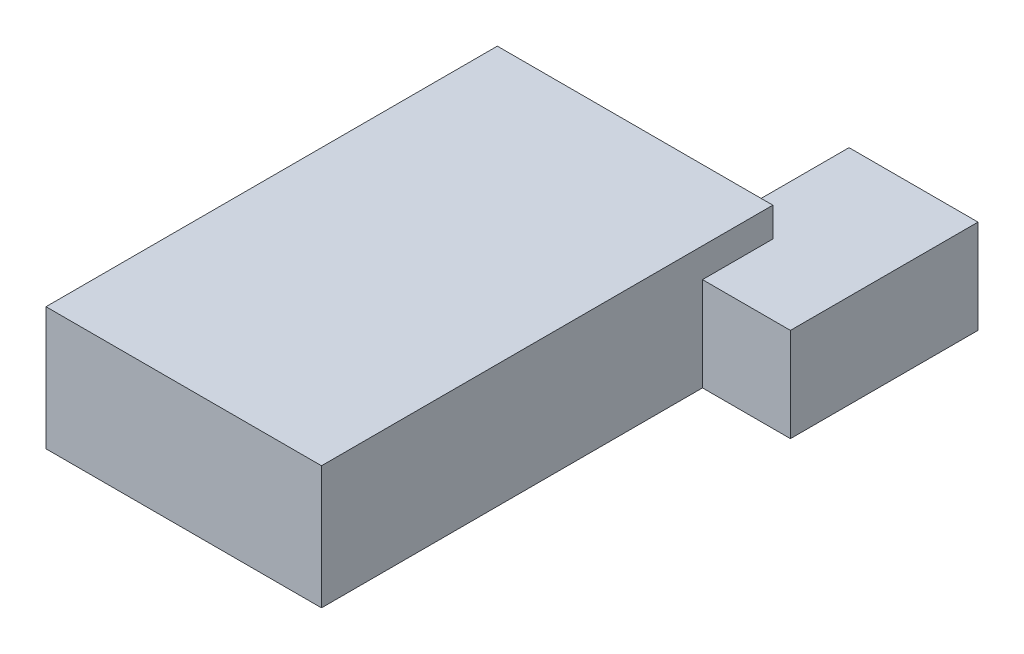
SolidWorks part; units mm, degrees
ref_plane "Front Plane" through (0, 0, 0) normal (0, 0, 1) x (1, 0, 0)
ref_plane "Top Plane" through (0, 0, 0) normal (0, 1, 0) x (1, 0, 0)
ref_plane "Right Plane" through (0, 0, 0) normal (1, 0, 0) x (0, 0, -1)
sketch "Sketch1" plane through (0, 0, 0) normal (0, 1, 0) x (1, 0, 0)
  line L1 (-4500, -7500) -> (4500, -7500)
  line L2 (-4500, -7500) -> (-4500, 7500)
  line L3 (-4500, 7500) -> (4500, 7500)
  line L4 (4500, -7500) -> (4500, 7500)
  line L5 (-4500, -7500) -> (4500, 7500) construction
  line L6 (-4500, 7500) -> (4500, -7500) construction
  point P0 (0, 0)
  dimension "D1" = 15000
  dimension "D2" = 9000
extrude "Boss-Extrude1" add sketch "Sketch1" along normal blind 4000
sketch "Sketch2" plane through (0, 0, -7500) normal (0, 0, -1) x (-1, 0, 0)
  line L1 (-4500, 0) -> (-3500, 0)
  line L2 (-4500, 0) -> (-4500, 3000)
  line L3 (-4500, 3000) -> (-3500, 3000)
  line L4 (-3500, 0) -> (-3500, 3000)
  line L5 (-4500, 3000) -> (-7500, 3000)
  line L6 (-4500, 3000) -> (-4500, 0)
  line L7 (-4500, 0) -> (-7500, 0)
  line L8 (-7500, 3000) -> (-7500, 0)
  line M1 (-4500, 0) -> (4500, 0)
  line M4 (-4500, 4000) -> (-4500, 0)
  dimension "D1" = 4000
  dimension "D2" = 1000
  dimension "3m" = 3000
extrude "Boss-Extrude2" add sketch "Sketch2" along normal blind 4000 and the other way blind 2000 contours L5 L8 L7 M4 | L4 L3 M1 M4 region at (4000, 1500, -7500) region at (6000, 1500, -7500)
sketch "Sketch3" plane through (0, 0, 0) normal (0, -1, 0) x (1, 0, 0)
  line L0 (3500, -11500) -> (7500, -11500) construction
  line L1 (10500, -11500) -> (-500, -11500)
  line L2 (10500, -11500) -> (10500, -4500)
  line L3 (10500, -4500) -> (-500, -4500)
  line L4 (-500, -11500) -> (-500, -4500)
  point P5 (3500, -11500)
  point P12 (7500, -11500)
  dimension "D1" = 11000
  dimension "D2" = 4000
  dimension "D3" = 7000
extrude "Boss-Extrude3" add sketch "Sketch3" along normal blind 12500
sketch "Sketch4" plane through (0, -12500, 0) normal (0, -1, 0) x (1, 0, 0)
  line L1 (10500, -11500) -> (3500, -11500)
  line L2 (10500, -11500) -> (10500, -7500)
  line L3 (10500, -7500) -> (3500, -7500)
  line L4 (3500, -11500) -> (3500, -7500)
  dimension "D1" = 7000
  dimension "D2" = 4000
extrude "Boss-Extrude4" add sketch "Sketch4" along normal blind 1500
sketch "Sketch5" plane through (0, 0, -4500) normal (0, 0, 1) x (1, 0, 0)
  line L1 (-500, -12500) -> (9500, -12500)
  line L2 (-500, -12500) -> (-500, -8500)
  line L3 (-500, -8500) -> (9500, -8500)
  line L4 (9500, -12500) -> (9500, -8500)
  dimension "D1" = 10000
  dimension "D2" = 4000
extrude "Boss-Extrude5" add sketch "Sketch5" along normal blind 12000
sketch "Sketch6" plane through (9500, 0, 0) normal (1, 0, 0) x (0, 0, -1)
  line L0 (-7250, -11500) -> (-7500, -11500) construction
  line L1 (-7500, -12500) -> (-7500, -8500) construction
  line L2 (-7500, -12500) -> (4500, -12500) construction
  circle A0 centre (-5250, -11500) radius 2000
  dimension "D1" = 4000
  dimension "D2" = 1000
  dimension "D3" = 250
extrude "Boss-Extrude6" add sketch "Sketch6" along normal blind 6000
ref_plane "Plane1" through (0, -10500, 0) normal (0, -1, 0) x (-1, 0, 0)
sketch "Sketch9" plane through (0, -10500, 0) normal (0, -1, 0) x (-1, 0, 0)
  circle A0 centre (-22728.4161, -5250) radius 7500
  point P2 (-15500, -3250)
  point P3 (-15500, -7250)
  dimension "D1" = 15000
extrude "Boss-Extrude8" add sketch "Sketch9" against normal blind 4000 and the other way blind 10000
sketch "Sketch10" plane through (0, -6500, 0) normal (0, 1, 0) x (1, 0, 0)
  line L0 (15228.4161, -5250) -> (30228.4161, -5250)
  arc A0 (15500, -3250) -> (15500, -7250) centre (22728.4161, -5250) ccw construction
  circle A1 centre (22728.4161, -5250) radius 7500 construction
  arc A2 (15228.4161, -5250) -> (30228.4161, -5250) centre (22728.4161, -5250) cw
revolve "Revolve5" add sketch "Sketch10" angle 180 about L0
sketch "Sketch12" plane through (-500, 0, 0) normal (-1, 0, 0) x (0, 0, 1)
  arc A0 (3517.9492, -12500) -> (6982.0508, -12500) centre (5250, -11500) ccw construction
  arc A1 (6982.0508, -12500) -> (3517.9492, -12500) centre (5250, -11500) ccw construction
  arc A2 (3517.9492, -12500) -> (6982.0508, -12500) centre (5250, -11500) ccw
  arc A3 (6982.0508, -12500) -> (3517.9492, -12500) centre (5250, -11500) ccw
extrude "Boss-Extrude9" add sketch "Sketch12" along normal blind 40000
sketch "Sketch16" plane through (0, -10500, 0) normal (0, -1, 0) x (-1, 0, 0)
  circle A0 centre (47728.4161, -5250) radius 7500
  point P2 (40500, -3250)
  point P3 (40500, -7250)
  dimension "15m" = 15000
extrude "Boss-Extrude11" add sketch "Sketch16" against normal up to surface (10500 mm away) and the other way blind 20000 up to face at (-166.6667, 0, -1500)
sketch "Sketch18" plane through (-500, 0, 0) normal (1, 0, 0) x (0, 0, -1)
  line L1 (-3517.9492, -12500) -> (-6982.0508, -12500)
  line L2 (-3517.9492, -12500) -> (-6982.0508, -12500)
  arc A1 (-6982.0508, -12500) -> (-3517.9492, -12500) centre (-5250, -11500) ccw
  arc A2 (-6982.0508, -12500) -> (-3517.9492, -12500) centre (-5250, -11500) ccw
  dimension "D1" = 0
extrude "Boss-Extrude12" add sketch "Sketch18" along normal up to surface (10000 mm away) up to face at (9500, -13000, 5250)
fillet "Fillet1" radius 1000 1 edges at (22728.4161, -20500, -2250)
fillet "Fillet2" radius 1000 1 edges at (-47728.4161, -30500, -2250)
sketch "Sketch19" plane through (0, 0, 0) normal (0, 1, 0) x (1, 0, 0)
  line L1 (10500, 11500) -> (7500, 11500)
  line L2 (10500, 11500) -> (10500, 5500)
  line L3 (10500, 5500) -> (7500, 5500)
  line L4 (7500, 11500) -> (7500, 5500)
extrude "Cut-Extrude1" cut sketch "Sketch19" against normal up to surface (8500 mm away) up to face at (4500, -8500, 1500)
sketch "Sketch20" plane through (0, 0, -5500) normal (0, 0, -1) x (-1, 0, 0)
  line L0 (-10500, -8500) -> (-7500, -7500)
  line L1 (-7500, 3000) -> (-7500, -8500) construction
  line L2 (-7500, -8500) -> (-10500, -8500) construction
  line L3 (-7500, -8500) -> (-10500, -8500)
  line L4 (-7500, -7500) -> (-7500, -8500)
  line L9 (-7500, -8500) -> (-7500, 0)
  line L10 (-7500, 0) -> (-10500, 0)
  line L11 (-10500, 0) -> (-10500, -8500)
  line L12 (-10500, -8500) -> (-7500, -8500)
  line L13 (-7500, -8500) -> (-7500, 0)
  line L14 (-7500, 0) -> (-10500, 0)
  line L15 (-10500, 0) -> (-10500, -8500)
  line L16 (-10500, -8500) -> (-7500, -8500)
  line M5 (-7500, -8500) -> (-7500, 0)
  line M6 (-7500, 0) -> (-10500, 0)
  line M7 (-10500, 0) -> (-10500, -8500)
  dimension "D1" = 1000
  dimension "D2" = 0
extrude "Cut-Extrude2" cut sketch "Sketch20" against normal through all both and the other way through all contours L0 M7 M5 M6 region at (9031.25, -4005.2083, -5500)
ref_plane "Plane3" through (0, 0, 0) normal (0, -1, 0) x (-1, 0, 0)
sketch "Sketch22" plane through (0, 0, -5500) normal (0, 0, 1) x (1, 0, 0)
  line L0 (-4500, 0) -> (4500, 0) construction
  line L1 (-4500, 0) -> (4500, 0)
  line L2 (4500, 0) -> (7500, 0)
extrude "Cut-Extrude5" cut sketch "Sketch22" against normal through all and the other way through all flip side to cut body kept at (-4500, 0, -7500)
shell "Shell1" thickness 200 removed face at (6000, 0, -8500) removed face at (1642.8571, 0, -4071.4286) outward yes
sketch "Sketch23" plane through (0, 3000, 0) normal (0, -1, 0) x (1, 0, 0)
  line L0 (3500, -7500) -> (4500, -7500)
  line L1 (4500, -7500) -> (4500, -7700)
  line L2 (4500, -7700) -> (3500, -7700)
  line L3 (3500, -7500) -> (3500, -7700)
  line L4 (3500, -7700) -> (3300, -7700) construction
  line L5 (4500, -5500) -> (4500, -6300)
  line L6 (4500, 7500) -> (4500, -7500) construction
  line L7 (4500, -7300) -> (4500, -7500)
  line L8 (4500, -7300) -> (4700, -7300)
  line L9 (4700, -7300) -> (4700, -7700)
  line L10 (4700, -7700) -> (4500, -7700)
  line L11 (4500, -6300) -> (4700, -6300)
  line L12 (4700, -6300) -> (4700, -5500)
  line L13 (4500, -5500) -> (7500, -5500) construction
  line L14 (4500, -5500) -> (4700, -5500)
  point P14 (4700, -7252.0117)
  line M5 (4500, -5500) -> (4500, -7500)
  line M6 (4500, -7500) -> (3500, -7500)
  line M7 (3500, -7500) -> (3500, -11500)
  line M10 (7500, -5500) -> (4500, -5500)
  dimension "D1" = 1000
  dimension "D2" = 200
extrude "Boss-Extrude13" add sketch "Sketch23" along normal up to surface (3000 mm away) contours L10 L9 L8 L1 M5 | L2 L1 M6 M7 | L11 L12 M10 M5 region at (4600, 3000, -5900) region at (4000, 3000, -7600) region at (4600, 3000, -7500) up to face at (3100, 0, -5385)
sketch "Sketch24" plane through (4500, 0, 0) normal (-1, 0, 0) x (0, 0, 1)
  line L0 (-6300, 0) -> (-6300, 3000) construction
  line L1 (-7300, 3000) -> (-6300, 3000)
  line L2 (-7300, 3000) -> (-7300, 2300)
  line L3 (-7300, 2300) -> (-6300, 2300)
  line L4 (-6300, 3000) -> (-6300, 2300)
  line L5 (-6300, 2300) -> (-6300, 0) construction
  dimension "D1" = 2300
extrude "Boss-Extrude14" add sketch "Sketch24" against normal up to surface (200 mm away) up to face at (4700, 1500, -5900)
